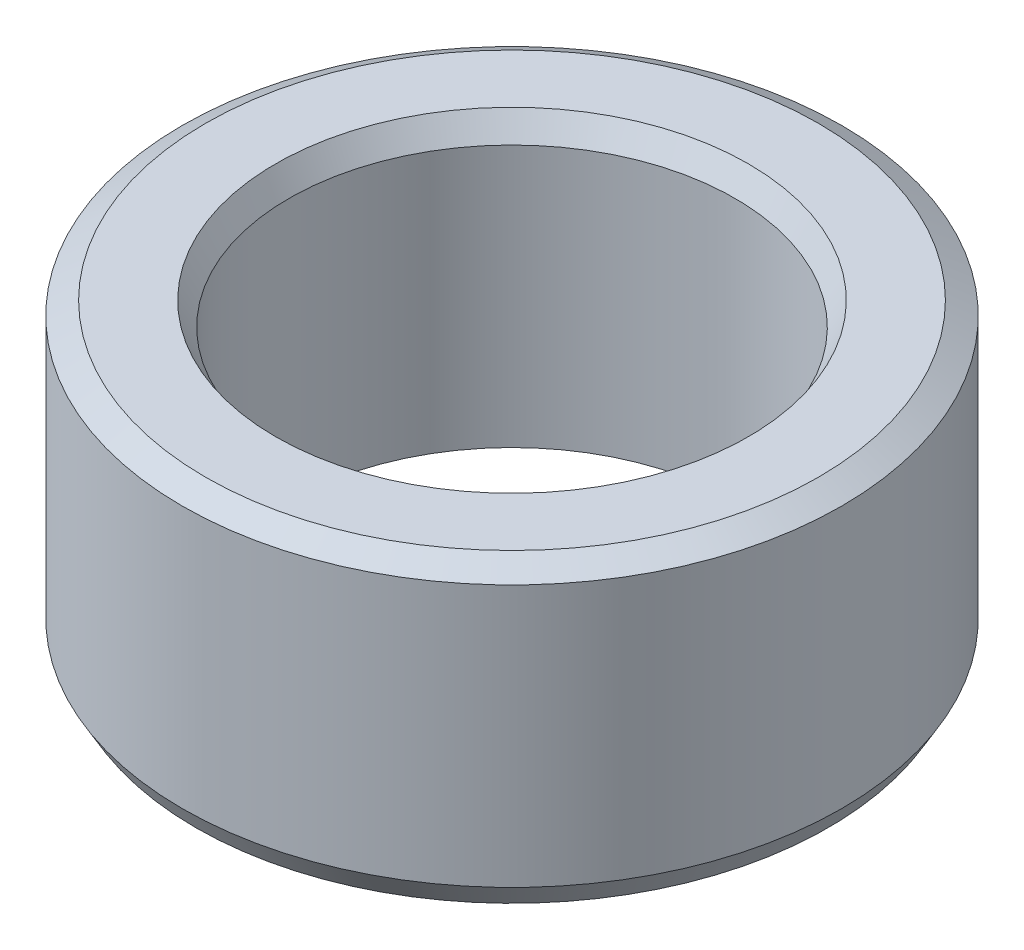
SolidWorks part; units mm, degrees
ref_plane "Front Plane" through (0, 0, 0) normal (0, 0, 1) x (1, 0, 0)
ref_plane "Top Plane" through (0, 0, 0) normal (0, 1, 0) x (1, 0, 0)
ref_plane "Right Plane" through (0, 0, 0) normal (1, 0, 0) x (0, 0, -1)
sketch "Sketch1" plane through (0, 0, 0) normal (0, 1, 0) x (1, 0, 0)
  circle A0 centre (0, 0) radius 40
  dimension "SLEEVE_OD" = 80
extrude "Boss-Extrude1" add sketch "Sketch1" along normal blind 36.2287
sketch "Sketch2" plane through (0, 0, 0) normal (0, 1, 0) x (1, 0, 0)
  circle A0 centre (0, 0) radius 27.0538
  dimension "BORE_D" = 54.1076
extrude "Cut-Extrude1" cut sketch "Sketch2" along normal through all
chamfer "Chamfer1" distance 1.6264 angle 60 4 edges at (0, 36.2287, 27.0538) (0, 0, 27.0538) (0, 0, 40) (0, 36.2287, 40) first distance on face at (0, 36.2287, 27.0538) first distance on face at (0, 0, 27.0538) first distance on face at (0, 36.2287, 40)
